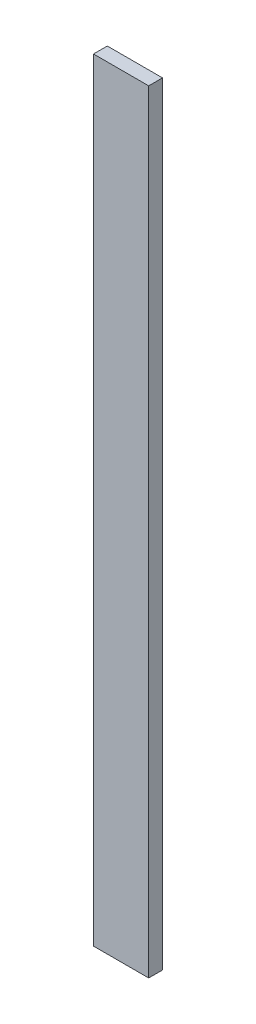
SolidWorks part; units mm, degrees
material "Pin"
ref_plane "Front" through (0, 0, 0) normal (0, 0, 1) x (1, 0, 0)
ref_plane "Top" through (0, 0, 0) normal (0, 1, 0) x (1, 0, 0)
ref_plane "Right" through (0, 0, 0) normal (1, 0, 0) x (0, 0, -1)
sketch "Esquisse2" plane through (0, 0, 0) normal (0, 0, 1) x (1, 0, 0)
  line L1 (-12.7, 177.8) -> (12.7, 177.8)
  line L2 (-12.7, 177.8) -> (-12.7, -177.8)
  line L3 (-12.7, -177.8) -> (12.7, -177.8)
  line L4 (12.7, 177.8) -> (12.7, -177.8)
  line L5 (-12.7, 177.8) -> (12.7, -177.8) construction
  line L6 (-12.7, -177.8) -> (12.7, 177.8) construction
  point P0 (0, 0)
  dimension "D1" = 355.6
  dimension "D2" = 25.4
extrude "Boss.-Extru.1" add sketch "Esquisse2" along normal blind 6.35
